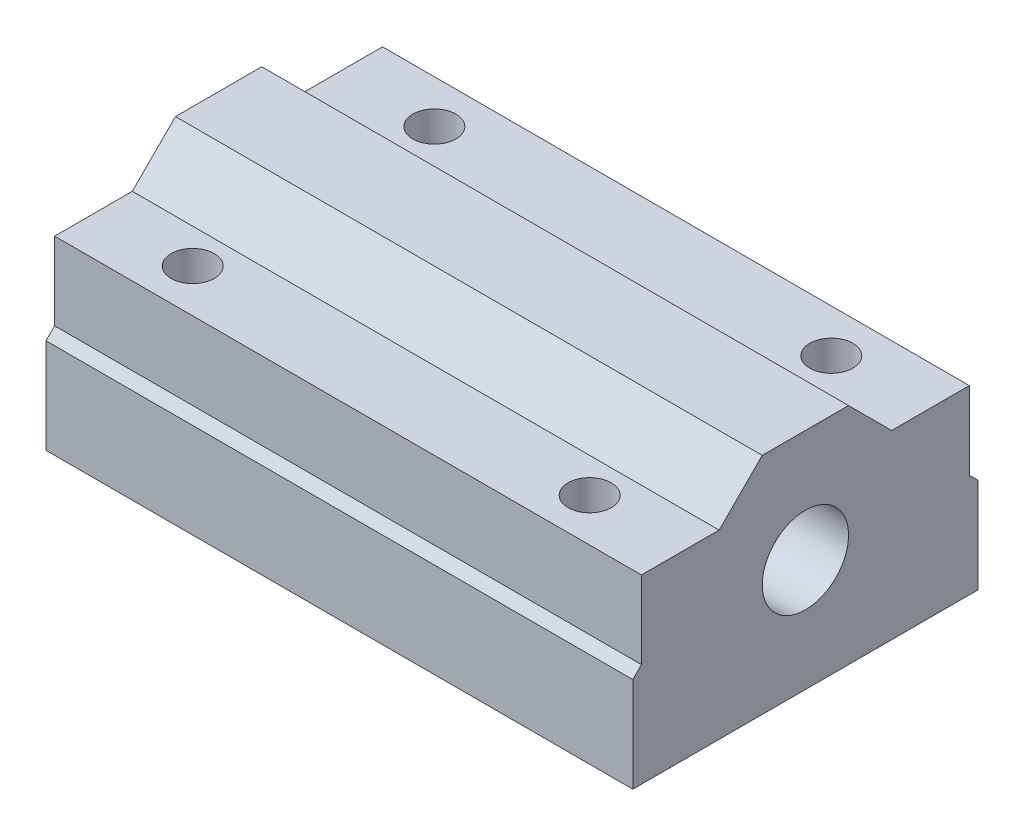
SolidWorks part; units mm, degrees
ref_plane "Спереди" through (0, 0, 0) normal (0, 0, 1) x (1, 0, 0)
ref_plane "Сверху" through (0, 0, 0) normal (0, 1, 0) x (1, 0, 0)
ref_plane "Справа" through (0, 0, 0) normal (1, 0, 0) x (0, 0, -1)
sketch "Эскиз1" plane through (0, 0, 0) normal (0, 1, 0) x (1, 0, 0)
  line L0 (11, 40) -> (11, 0) construction
  line L1 (0, 0) -> (68, 0)
  line L2 (0, 0) -> (0, 40)
  line L3 (0, 40) -> (68, 40)
  line L4 (68, 0) -> (68, 40)
  line L5 (57, 40) -> (57, 0) construction
  circle A0 centre (11, 34) radius 2.5
  circle A1 centre (11, 6) radius 2.5
  circle A2 centre (57, 34) radius 2.5
  circle A3 centre (57, 6) radius 2.5
  dimension "D4" = 5
  dimension "D5" = 5
  dimension "D9" = 6
  dimension "D1" = 68
  dimension "D2" = 40
  dimension "D3" = 11
  dimension "D6" = 6
  dimension "D7" = 6
  dimension "D8" = 11
  dimension "D10" = 6
extrude "Бобышка-Вытянуть1" add sketch "Эскиз1" along normal blind 26
sketch "Эскиз2" plane through (0, 0, 0) normal (-1, 0, 0) x (0, 0, 1)
  line L0 (-40, 13) -> (0, 13) construction
  line L1 (-40, 26) -> (-40, 0) construction
  line L2 (0, 26) -> (0, 0) construction
  line L3 (-20, 26) -> (-20, 0) construction
  line L4 (-40, 26) -> (0, 26) construction
  line L5 (-40, 0) -> (0, 0) construction
  circle A0 centre (-20, 13) radius 5
extrude "Вырез-Вытянуть1" cut sketch "Эскиз2" against normal blind 76
sketch "Эскиз3" plane through (0, 26, 0) normal (0, 1, 0) x (1, 0, 0)
  line L0 (68, 0) -> (68, 40) construction
  line L1 (0, 40) -> (68, 40)
  line L2 (0, 40) -> (0, 30)
  line L3 (0, 30) -> (68, 30)
  line L4 (68, 40) -> (68, 30)
  line L6 (0, 0) -> (68, 0)
  line L7 (0, 0) -> (0, 10)
  line L8 (0, 10) -> (68, 10)
  line L9 (68, 0) -> (68, 10)
  dimension "D1" = 10
  dimension "D2" = 10
extrude "Вырез-Вытянуть2" cut sketch "Эскиз3" against normal blind 5
chamfer "Фаска1" distance 5 angle 45 1 edges at (34, 26, -30)
chamfer "Фаска2" distance 5 angle 45 1 edges at (34, 26, -10)
sketch "Эскиз4" plane through (0, 21, 0) normal (0, 1, 0) x (1, 0, 0)
  line L0 (68, 30) -> (68, 40) construction
  line L1 (0, 40) -> (68, 40)
  line L2 (0, 40) -> (0, 39)
  line L3 (0, 39) -> (68, 39)
  line L4 (68, 40) -> (68, 39)
  line L5 (68, 0) -> (68, 10) construction
  line L6 (0, 0) -> (68, 0)
  line L7 (0, 0) -> (0, 1)
  line L8 (0, 1) -> (68, 1)
  line L9 (68, 0) -> (68, 1)
  dimension "D1" = 1
  dimension "D2" = 1
extrude "Вырез-Вытянуть3" cut sketch "Эскиз4" against normal blind 9
chamfer "Фаска3" distance 1 angle 45 1 edges at (34, 12, -40)
chamfer "Фаска4" distance 1 angle 45 1 edges at (34, 12, 0)
